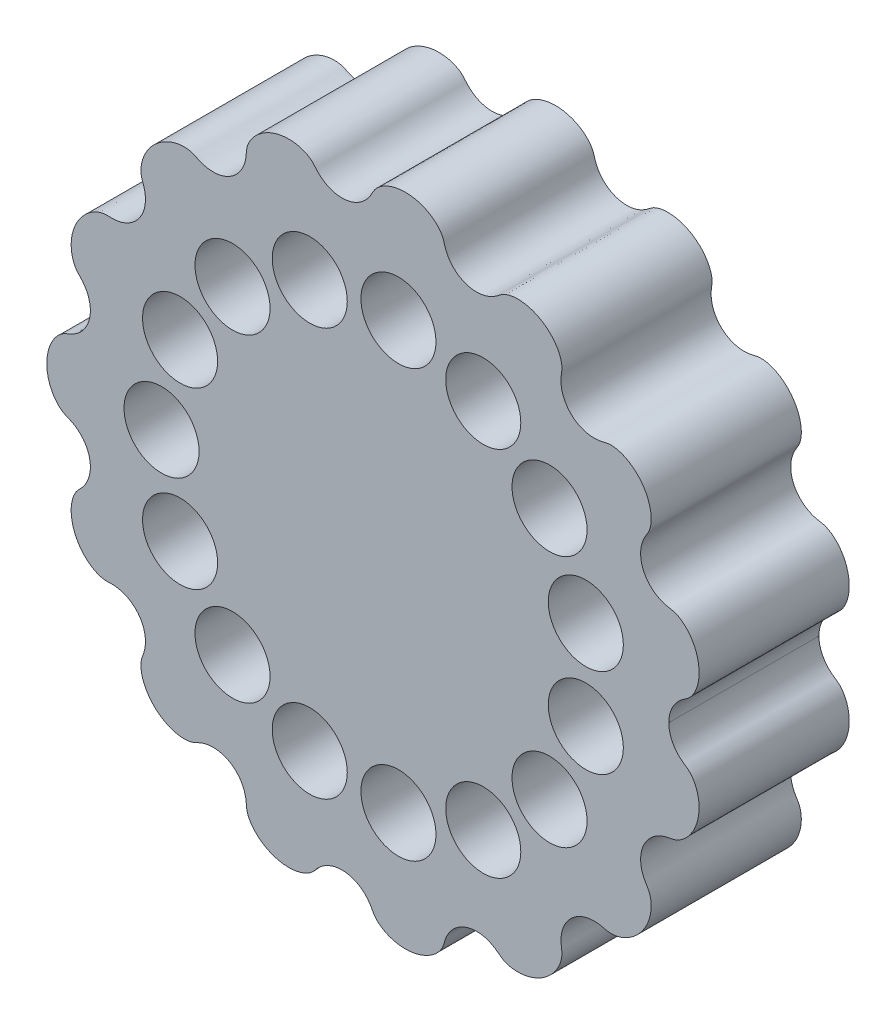
SolidWorks part; units mm, degrees
material "ABS"
ref_plane "Front Plane" through (0, 0, 0) normal (0, 0, 1) x (1, 0, 0)
ref_plane "Top Plane" through (0, 0, 0) normal (0, 1, 0) x (1, 0, 0)
ref_plane "Right Plane" through (0, 0, 0) normal (1, 0, 0) x (0, 0, -1)
sketch "Sketch2" plane through (0, 0, 0) normal (0, 0, 1) x (1, 0, 0)
  line L0 (0, 0) -> (18.3781, 0) construction
  line L1 (0, 0) -> (-12.7, 0) construction
  line L6 (0, 0) -> (-26.7529, 0) construction
  circle A0 centre (0, 0) radius 9
  circle A1 centre (-12.7, 0) radius 2.2225
  circle A10 centre (-11.602, 5.1656) radius 2.2225
  circle A11 centre (-8.498, 9.4379) radius 2.2225
  circle A12 centre (-3.9245, 12.0784) radius 2.2225
  circle A13 centre (1.3275, 12.6304) radius 2.2225
  circle A14 centre (6.35, 10.9985) radius 2.2225
  circle A15 centre (10.2745, 7.4649) radius 2.2225
  circle A16 centre (12.4225, 2.6405) radius 2.2225
  circle A17 centre (12.4225, -2.6405) radius 2.2225
  circle A18 centre (10.2745, -7.4649) radius 2.2225
  circle A19 centre (6.35, -10.9985) radius 2.2225
  circle A20 centre (1.3275, -12.6304) radius 2.2225
  circle A21 centre (-3.9245, -12.0784) radius 2.2225
  circle A22 centre (-8.498, -9.4379) radius 2.2225
  circle A23 centre (-11.602, -5.1656) radius 2.2225
  spline S0 degree 4 poles (18.7633, 4.8586) (18.8566, 4.6949) (19.0126, 4.3502) (19.1295, 3.8883) (19.146, 3.3193) (19.0772, 2.8818) (18.9864, 2.5766) (18.8762, 2.3288) (18.7622, 2.1358) (18.6445, 1.9821) (18.5309, 1.8645) (18.4127, 1.7724) (18.2984, 1.6976) (18.1631, 1.6053) (18.0131, 1.4864) (17.8313, 1.3119) (17.6678, 1.103) (17.5417, 0.8858) (17.4501, 0.6688) (17.4009, 0.5099) (17.3699, 0.3735) (17.3511, 0.2546) (17.3405, 0.1491) (17.3351, 0.0404) (17.335, -0.0379) (17.3404, -0.1482) (17.3511, -0.2558) (17.3711, -0.3808) (17.4057, -0.5292) (17.4608, -0.6993) (17.5431, -0.8835) (17.6435, -1.0585) (17.7605, -1.2214) (17.8868, -1.3648) (18.0188, -1.4893) (18.152, -1.5968) (18.284, -1.6887) (18.4068, -1.7677) (18.5101, -1.8484) (18.6114, -1.9469) (18.7103, -2.0649) (18.8119, -2.2151) (18.9788, -2.5318) (19.1284, -3.0222) (19.1691, -3.6778) (19.0197, -4.3616) (18.7658, -4.895) (18.5029, -5.2499) (18.2908, -5.4667) (18.0909, -5.625) (17.936, -5.7218) (17.7996, -5.7887) (17.6725, -5.8365) (17.5499, -5.8688) (17.4098, -5.8911) (17.2557, -5.9192) (17.0952, -5.96) (16.9297, -6.0153) (16.7182, -6.1072) (16.4691, -6.2552) (16.2082, -6.4745) (15.9606, -6.7851) (15.777, -7.1489) (15.6723, -7.5479) (15.6565, -7.9135) (15.698, -8.2228) (15.7641, -8.4609) (15.8302, -8.6338) (15.9057, -8.7908) (15.9865, -8.9326) (16.0678, -9.0566) (16.1353, -9.1714) (16.1945, -9.3026) (16.2418, -9.4503) (16.2782, -9.6273) (16.3107, -9.9874) (16.2563, -10.505) (16.0255, -11.1471) (15.5906, -11.7382) (15.1094, -12.1391) (14.6943, -12.3573) (14.4005, -12.4606) (14.1434, -12.5135) (13.9574, -12.5296) (13.7955, -12.524) (13.646, -12.4991) (13.511, -12.464) (13.3614, -12.4266) (13.1944, -12.3981) (13.0154, -12.381) (12.8253, -12.3797) (12.5738, -12.4026) (12.2655, -12.4754) (11.9355, -12.6193) (11.6068, -12.8541) (11.3394, -13.1429) (11.1399, -13.4677) (11.021, -13.7866) (10.9639, -14.0781) (10.9493, -14.3167) (10.9547, -14.4996) (10.9719, -14.6649) (10.9953, -14.8125) (11.0138, -14.9707) (11.0079, -15.1399) (10.9777, -15.3255) (10.9213, -15.5246) (10.826, -15.7601) (10.6793, -16.0232) (10.4202, -16.3707) (10.0022, -16.7545) (9.5088, -17.0394) (8.9674, -17.2095) (8.5368, -17.2602) (8.2356, -17.2556) (7.9841, -17.2204) (7.7834, -17.1697) (7.6075, -17.1031) (7.4581, -17.0235) (7.3304, -16.9284) (7.2142, -16.8343) (7.0797, -16.7369) (6.924, -16.6408) (6.7101, -16.534) (6.4291, -16.4378) (6.0935, -16.3813) (5.7124, -16.3917) (5.3285, -16.4789) (4.9609, -16.6461) (4.6712, -16.86) (4.454, -17.0906) (4.3085, -17.2969) (4.2145, -17.4622) (4.1399, -17.6257) (4.0811, -17.7846) (4.0386, -17.9329) (4.0016, -18.0673) (3.9484, -18.2093) (3.8722, -18.3523) (3.7653, -18.5053) (3.5909, -18.7015) (3.3546, -18.9043) (2.9581, -19.1547) (2.3703, -19.371) (1.6409, -19.4521) (0.9694, -19.3309) (0.494, -19.1192) (0.1984, -18.911) (0.0633, -18.791) (-0.0409, -18.6762) (-0.125, -18.5593) (-0.1906, -18.4434) (-0.2573, -18.311) (-0.3397, -18.1701) (-0.438, -18.0263) (-0.5547, -17.8825) (-0.7278, -17.7063) (-0.975, -17.5157) (-1.2995, -17.3465) (-1.6974, -17.2377) (-2.1042, -17.2148) (-2.4971, -17.274) (-2.8174, -17.3902) (-3.0701, -17.532) (-3.2554, -17.6692) (-3.3861, -17.7848) (-3.5017, -17.9035) (-3.6031, -18.0229) (-3.6924, -18.133) (-3.7817, -18.2231) (-3.8867, -18.3093) (-4.0128, -18.3939) (-4.1741, -18.4797) (-4.4111, -18.5737) (-4.7049, -18.6489) (-5.1436, -18.6992) (-5.7326, -18.6523) (-6.3023, -18.4708) (-6.8174, -18.1627) (-7.1549, -17.854) (-7.3507, -17.6166) (-7.4876, -17.3991) (-7.5669, -17.236) (-7.6196, -17.0913) (-7.6543, -16.9544) (-7.6725, -16.8247) (-7.6795, -16.6788) (-7.6932, -16.5185) (-7.7196, -16.3494) (-7.7615, -16.1729) (-7.8384, -15.9445) (-7.9726, -15.6719) (-8.1825, -15.3834) (-8.486, -15.1097) (-8.8424, -14.9039) (-9.2312, -14.778) (-9.586, -14.7404) (-9.8891, -14.7605) (-10.1254, -14.8081) (-10.2992, -14.8601) (-10.4589, -14.9217) (-10.6045, -14.9901) (-10.7343, -15.0569) (-10.8558, -15.106) (-10.9917, -15.1445) (-11.1433, -15.1711) (-11.3243, -15.184) (-11.5811, -15.1742) (-11.8846, -15.1233) (-12.3207, -14.9854) (-12.845, -14.6933) (-13.2871, -14.2907) (-13.6221, -13.8041) (-13.798, -13.399) (-13.8798, -13.107) (-13.9168, -12.8547) (-13.9232, -12.6721) (-13.913, -12.5206) (-13.8908, -12.3866) (-13.8575, -12.2643) (-13.8068, -12.1318) (-13.7541, -11.9843) (-13.7091, -11.8249) (-13.6743, -11.6539) (-13.6481, -11.4248) (-13.6517, -11.135) (-13.7112, -10.7995) (-13.8564, -10.4297) (-14.0796, -10.0888) (-14.3728, -9.7987) (-14.6815, -9.6022) (-14.9702, -9.4834) (-15.2094, -9.4216) (-15.3922, -9.3924) (-15.5659, -9.3793) (-15.7291, -9.3784) (-15.8771, -9.3868) (-16.0104, -9.3879) (-16.1536, -9.3736) (-16.3051, -9.3407) (-16.4766, -9.2837) (-16.8047, -9.1318) (-17.2258, -8.8259) (-17.6664, -8.3049) (-17.9609, -7.6328) (-18.0675, -7.0156) (-18.0489, -6.547) (-17.9914, -6.2409) (-17.9088, -5.9918) (-17.8296, -5.8227) (-17.7439, -5.6853) (-17.661, -5.5845) (-17.5943, -5.5141) (-17.5308, -5.4492) (-17.4724, -5.3879) (-17.4019, -5.309) (-17.3219, -5.2104) (-17.23, -5.0812) (-17.1338, -4.9172) (-17.0279, -4.688) (-16.9368, -4.3846) (-16.8964, -4.0268) (-16.9354, -3.6248) (-17.0518, -3.2488) (-17.2333, -2.9135) (-17.4501, -2.6512) (-17.6739, -2.4559) (-17.8733, -2.324) (-18.0344, -2.2373) (-18.1861, -2.1695) (-18.3256, -2.1159) (-18.4719, -2.0529) (-18.6155, -1.9632) (-18.7611, -1.8442) (-18.9053, -1.6958) (-19.0616, -1.4955) (-19.192, -1.2774) (-19.2944, -1.0552) (-19.3719, -0.8334) (-19.4214, -0.6522) (-19.4539, -0.4901) (-19.4739, -0.3535) (-19.4855, -0.2338) (-19.4917, -0.1326) (-19.4948, -0.037) (-19.4948, 0.0364) (-19.4917, 0.1316) (-19.4856, 0.232) (-19.4742, 0.351) (-19.4544, 0.4867) (-19.4225, 0.6475) (-19.3737, 0.8276) (-19.2973, 1.048) (-19.1964, 1.2688) (-19.0681, 1.4857) (-18.9143, 1.6852) (-18.7725, 1.8335) (-18.6329, 1.9498) (-18.5003, 2.0363) (-18.3706, 2.0977) (-18.2504, 2.1445) (-18.1062, 2.2036) (-17.9419, 2.2842) (-17.733, 2.4112) (-17.4958, 2.6047) (-17.2705, 2.8611) (-17.0558, 3.2276) (-16.9099, 3.6914) (-16.895, 4.0854) (-16.9436, 4.3777) (-16.984, 4.5249) knots 0 0 0 0 0 0.009284 0.018569 0.023211 0.027854 0.031033 0.034213 0.036543 0.038874 0.040556 0.042237 0.043918 0.0456 0.048628 0.051656 0.056303 0.058626 0.060948 0.063272 0.064433 0.065595 0.066886 0.068176 0.069432 0.070688 0.071943 0.073199 0.07572 0.07824 0.080694 0.083148 0.08563 0.088113 0.090095 0.092076 0.094058 0.09604 0.097282 0.098525 0.10101 0.103607 0.106204 0.116127 0.126049 0.135533 0.140274 0.145016 0.147725 0.150434 0.152813 0.154002 0.155191 0.157122 0.159052 0.160982 0.162912 0.165276 0.167641 0.172327 0.177141 0.181961 0.187087 0.192259 0.197312 0.199858 0.202403 0.204413 0.206423 0.208433 0.210443 0.211712 0.212982 0.21552 0.21806 0.2206 0.230761 0.24092 0.251197 0.256273 0.261349 0.26392 0.26649 0.269181 0.270527 0.271873 0.273958 0.276043 0.278128 0.280213 0.282806 0.285398 0.290549 0.295754 0.300413 0.305158 0.309821 0.314419 0.31708 0.319741 0.321582 0.323422 0.325263 0.327104 0.329419 0.331734 0.334508 0.337282 0.34191 0.346537 0.355792 0.365046 0.369673 0.374301 0.377075 0.379849 0.382164 0.384479 0.38632 0.388161 0.390001 0.391842 0.394503 0.397165 0.401762 0.406425 0.41117 0.415829 0.421034 0.426185 0.428777 0.43137 0.433455 0.43554 0.437625 0.439711 0.441056 0.442402 0.445093 0.447663 0.450234 0.45531 0.460386 0.470663 0.480822 0.490983 0.493523 0.496063 0.498601 0.499871 0.50114 0.50315 0.50516 0.50717 0.50918 0.511725 0.514271 0.519324 0.524496 0.529623 0.534442 0.539256 0.543942 0.546307 0.548671 0.550601 0.552531 0.554461 0.556392 0.557581 0.55877 0.561149 0.563858 0.566567 0.571309 0.57605 0.585534 0.595456 0.600418 0.605379 0.607976 0.610573 0.613058 0.614301 0.615543 0.617525 0.619507 0.621488 0.62347 0.625953 0.628436 0.633343 0.638384 0.643407 0.648429 0.653471 0.658378 0.660861 0.663343 0.665325 0.667307 0.669288 0.67127 0.672513 0.673755 0.676241 0.678838 0.681434 0.686396 0.691357 0.701279 0.710763 0.715505 0.720246 0.722955 0.725664 0.728043 0.729232 0.730422 0.732352 0.734282 0.736212 0.738142 0.740507 0.742871 0.747557 0.752371 0.757191 0.762317 0.76749 0.772543 0.775088 0.777634 0.779644 0.781654 0.783663 0.785673 0.786943 0.788212 0.790751 0.793291 0.79583 0.805991 0.816151 0.826427 0.831503 0.83658 0.83915 0.841721 0.844412 0.845757 0.847103 0.848145 0.849188 0.85023 0.851273 0.853358 0.855443 0.858036 0.860629 0.865779 0.870984 0.875643 0.880389 0.885051 0.889649 0.89231 0.894972 0.896812 0.898653 0.900493 0.902334 0.904649 0.906964 0.909738 0.912513 0.91714 0.919454 0.921767 0.924081 0.926394 0.927551 0.928708 0.929865 0.931022 0.93217 0.933319 0.934467 0.935616 0.937913 0.94021 0.942507 0.944804 0.949398 0.952146 0.954894 0.957192 0.95949 0.961079 0.962667 0.964255 0.965844 0.968759 0.971674 0.976278 0.980873 0.985473 0.99248 1 1 1 1 1 construction
  spline S1 degree 4 poles (17.3355, 0) (17.3355, -0.022) (17.3364, -0.0661) (17.3404, -0.1482) (17.3511, -0.2558) (17.3711, -0.3808) (17.4057, -0.5292) (17.4608, -0.6993) (17.5431, -0.8835) (17.6435, -1.0585) (17.7605, -1.2214) (17.8868, -1.3648) (18.0188, -1.4893) (18.152, -1.5968) (18.284, -1.6887) (18.4068, -1.7677) (18.5101, -1.8484) (18.6114, -1.9469) (18.7103, -2.0649) (18.8119, -2.2151) (18.9788, -2.5318) (19.1284, -3.0222) (19.1691, -3.6778) (19.0197, -4.3616) (18.7658, -4.895) (18.5029, -5.2499) (18.2908, -5.4667) (18.0909, -5.625) (17.936, -5.7218) (17.7996, -5.7887) (17.6725, -5.8365) (17.5499, -5.8688) (17.4098, -5.8911) (17.2557, -5.9192) (17.0952, -5.96) (16.9297, -6.0153) (16.7182, -6.1072) (16.4691, -6.2552) (16.2082, -6.4745) (15.9606, -6.7851) (15.777, -7.1489) (15.6723, -7.5479) (15.6565, -7.9135) (15.698, -8.2228) (15.7641, -8.4609) (15.8302, -8.6338) (15.9057, -8.7908) (15.9865, -8.9326) (16.0678, -9.0566) (16.1353, -9.1714) (16.1945, -9.3026) (16.2418, -9.4503) (16.2782, -9.6273) (16.3107, -9.9874) (16.2563, -10.505) (16.0255, -11.1471) (15.5906, -11.7382) (15.1094, -12.1391) (14.6943, -12.3573) (14.4005, -12.4606) (14.1434, -12.5135) (13.9574, -12.5296) (13.7955, -12.524) (13.646, -12.4991) (13.511, -12.464) (13.3614, -12.4266) (13.1944, -12.3981) (13.0154, -12.381) (12.8253, -12.3797) (12.5738, -12.4026) (12.2655, -12.4754) (11.9355, -12.6193) (11.6068, -12.8541) (11.3394, -13.1429) (11.1399, -13.4677) (11.021, -13.7866) (10.9639, -14.0781) (10.9493, -14.3167) (10.9547, -14.4996) (10.9719, -14.6649) (10.9953, -14.8125) (11.0138, -14.9707) (11.0079, -15.1399) (10.9777, -15.3255) (10.9213, -15.5246) (10.826, -15.7601) (10.6793, -16.0232) (10.4202, -16.3707) (10.0022, -16.7545) (9.5088, -17.0394) (8.9674, -17.2095) (8.5368, -17.2602) (8.2356, -17.2556) (7.9841, -17.2204) (7.7834, -17.1697) (7.6075, -17.1031) (7.4581, -17.0235) (7.3304, -16.9284) (7.2142, -16.8343) (7.0797, -16.7369) (6.924, -16.6408) (6.7101, -16.534) (6.4291, -16.4378) (6.0935, -16.3813) (5.7124, -16.3917) (5.3285, -16.4789) (4.9609, -16.6461) (4.6712, -16.86) (4.454, -17.0906) (4.3085, -17.2969) (4.2145, -17.4622) (4.1399, -17.6257) (4.0811, -17.7846) (4.0386, -17.9329) (4.0016, -18.0673) (3.9484, -18.2093) (3.8722, -18.3523) (3.7653, -18.5053) (3.5909, -18.7015) (3.3546, -18.9043) (2.9581, -19.1547) (2.3703, -19.371) (1.6409, -19.4521) (0.9694, -19.3309) (0.494, -19.1192) (0.1984, -18.911) (0.0633, -18.791) (-0.0409, -18.6762) (-0.125, -18.5593) (-0.1906, -18.4434) (-0.2573, -18.311) (-0.3397, -18.1701) (-0.438, -18.0263) (-0.5547, -17.8825) (-0.7278, -17.7063) (-0.975, -17.5157) (-1.2995, -17.3465) (-1.6974, -17.2377) (-2.1042, -17.2148) (-2.4971, -17.274) (-2.8174, -17.3902) (-3.0701, -17.532) (-3.2554, -17.6692) (-3.3861, -17.7848) (-3.5017, -17.9035) (-3.6031, -18.0229) (-3.6924, -18.133) (-3.7817, -18.2231) (-3.8867, -18.3093) (-4.0128, -18.3939) (-4.1741, -18.4797) (-4.4111, -18.5737) (-4.7049, -18.6489) (-5.1436, -18.6992) (-5.7326, -18.6523) (-6.3023, -18.4708) (-6.8174, -18.1627) (-7.1549, -17.854) (-7.3507, -17.6166) (-7.4876, -17.3991) (-7.5669, -17.236) (-7.6196, -17.0913) (-7.6543, -16.9544) (-7.6725, -16.8247) (-7.6795, -16.6788) (-7.6932, -16.5185) (-7.7196, -16.3494) (-7.7615, -16.1729) (-7.8384, -15.9445) (-7.9726, -15.6719) (-8.1825, -15.3834) (-8.486, -15.1097) (-8.8424, -14.9039) (-9.2312, -14.778) (-9.586, -14.7404) (-9.8891, -14.7605) (-10.1254, -14.8081) (-10.2992, -14.8601) (-10.4589, -14.9217) (-10.6045, -14.9901) (-10.7343, -15.0569) (-10.8558, -15.106) (-10.9917, -15.1445) (-11.1433, -15.1711) (-11.3243, -15.184) (-11.5811, -15.1742) (-11.8846, -15.1233) (-12.3207, -14.9854) (-12.845, -14.6933) (-13.2871, -14.2907) (-13.6221, -13.8041) (-13.798, -13.399) (-13.8798, -13.107) (-13.9168, -12.8547) (-13.9232, -12.6721) (-13.913, -12.5206) (-13.8908, -12.3866) (-13.8575, -12.2643) (-13.8068, -12.1318) (-13.7541, -11.9843) (-13.7091, -11.8249) (-13.6743, -11.6539) (-13.6481, -11.4248) (-13.6517, -11.135) (-13.7112, -10.7995) (-13.8564, -10.4297) (-14.0796, -10.0888) (-14.3728, -9.7987) (-14.6815, -9.6022) (-14.9702, -9.4834) (-15.2094, -9.4216) (-15.3922, -9.3924) (-15.5659, -9.3793) (-15.7291, -9.3784) (-15.8771, -9.3868) (-16.0104, -9.3879) (-16.1536, -9.3736) (-16.3051, -9.3407) (-16.4766, -9.2837) (-16.8047, -9.1318) (-17.2258, -8.8259) (-17.6664, -8.3049) (-17.9609, -7.6328) (-18.0675, -7.0156) (-18.0489, -6.547) (-17.9914, -6.2409) (-17.9088, -5.9918) (-17.8296, -5.8227) (-17.7439, -5.6853) (-17.661, -5.5845) (-17.5943, -5.5141) (-17.5308, -5.4492) (-17.4724, -5.3879) (-17.4019, -5.309) (-17.3219, -5.2104) (-17.23, -5.0812) (-17.1338, -4.9172) (-17.0279, -4.688) (-16.9368, -4.3846) (-16.8964, -4.0268) (-16.9354, -3.6248) (-17.0518, -3.2488) (-17.2333, -2.9135) (-17.4501, -2.6512) (-17.6739, -2.4559) (-17.8733, -2.324) (-18.0344, -2.2373) (-18.1861, -2.1695) (-18.3256, -2.1159) (-18.4719, -2.0529) (-18.6155, -1.9632) (-18.7611, -1.8442) (-18.9053, -1.6958) (-19.0616, -1.4955) (-19.192, -1.2774) (-19.2944, -1.0552) (-19.3719, -0.8334) (-19.4214, -0.6522) (-19.4539, -0.4901) (-19.4739, -0.3535) (-19.4855, -0.2338) (-19.4917, -0.1326) (-19.494, -0.0608) (-19.4945, -0.0203) (-19.4945, 0) knots 0.068176 0.068176 0.068176 0.068176 0.068176 0.069432 0.070688 0.071943 0.073199 0.07572 0.07824 0.080694 0.083148 0.08563 0.088113 0.090095 0.092076 0.094058 0.09604 0.097282 0.098525 0.10101 0.103607 0.106204 0.116127 0.126049 0.135533 0.140274 0.145016 0.147725 0.150434 0.152813 0.154002 0.155191 0.157122 0.159052 0.160982 0.162912 0.165276 0.167641 0.172327 0.177141 0.181961 0.187087 0.192259 0.197312 0.199858 0.202403 0.204413 0.206423 0.208433 0.210443 0.211712 0.212982 0.21552 0.21806 0.2206 0.230761 0.24092 0.251197 0.256273 0.261349 0.26392 0.26649 0.269181 0.270527 0.271873 0.273958 0.276043 0.278128 0.280213 0.282806 0.285398 0.290549 0.295754 0.300413 0.305158 0.309821 0.314419 0.31708 0.319741 0.321582 0.323422 0.325263 0.327104 0.329419 0.331734 0.334508 0.337282 0.34191 0.346537 0.355792 0.365046 0.369673 0.374301 0.377075 0.379849 0.382164 0.384479 0.38632 0.388161 0.390001 0.391842 0.394503 0.397165 0.401762 0.406425 0.41117 0.415829 0.421034 0.426185 0.428777 0.43137 0.433455 0.43554 0.437625 0.439711 0.441056 0.442402 0.445093 0.447663 0.450234 0.45531 0.460386 0.470663 0.480822 0.490983 0.493523 0.496063 0.498601 0.499871 0.50114 0.50315 0.50516 0.50717 0.50918 0.511725 0.514271 0.519324 0.524496 0.529623 0.534442 0.539256 0.543942 0.546307 0.548671 0.550601 0.552531 0.554461 0.556392 0.557581 0.55877 0.561149 0.563858 0.566567 0.571309 0.57605 0.585534 0.595456 0.600418 0.605379 0.607976 0.610573 0.613058 0.614301 0.615543 0.617525 0.619507 0.621488 0.62347 0.625953 0.628436 0.633343 0.638384 0.643407 0.648429 0.653471 0.658378 0.660861 0.663343 0.665325 0.667307 0.669288 0.67127 0.672513 0.673755 0.676241 0.678838 0.681434 0.686396 0.691357 0.701279 0.710763 0.715505 0.720246 0.722955 0.725664 0.728043 0.729232 0.730422 0.732352 0.734282 0.736212 0.738142 0.740507 0.742871 0.747557 0.752371 0.757191 0.762317 0.76749 0.772543 0.775088 0.777634 0.779644 0.781654 0.783663 0.785673 0.786943 0.788212 0.790751 0.793291 0.79583 0.805991 0.816151 0.826427 0.831503 0.83658 0.83915 0.841721 0.844412 0.845757 0.847103 0.848145 0.849188 0.85023 0.851273 0.853358 0.855443 0.858036 0.860629 0.865779 0.870984 0.875643 0.880389 0.885051 0.889649 0.89231 0.894972 0.896812 0.898653 0.900493 0.902334 0.904649 0.906964 0.909738 0.912513 0.91714 0.919454 0.921767 0.924081 0.926394 0.927551 0.928708 0.929865 0.931022 0.931022 0.931022 0.931022 0.931022
  spline S2 degree 4 poles (17.3355, 0) (17.3355, 0.022) (17.3364, 0.0661) (17.3404, 0.1482) (17.3511, 0.2558) (17.3711, 0.3808) (17.4057, 0.5292) (17.4608, 0.6993) (17.5431, 0.8835) (17.6435, 1.0585) (17.7605, 1.2214) (17.8868, 1.3648) (18.0188, 1.4893) (18.152, 1.5968) (18.284, 1.6887) (18.4068, 1.7677) (18.5101, 1.8484) (18.6114, 1.9469) (18.7103, 2.0649) (18.8119, 2.2151) (18.9788, 2.5318) (19.1284, 3.0222) (19.1691, 3.6778) (19.0197, 4.3616) (18.7658, 4.895) (18.5029, 5.2499) (18.2908, 5.4667) (18.0909, 5.625) (17.936, 5.7218) (17.7996, 5.7887) (17.6725, 5.8365) (17.5499, 5.8688) (17.4098, 5.8911) (17.2557, 5.9192) (17.0952, 5.96) (16.9297, 6.0153) (16.7182, 6.1072) (16.4691, 6.2552) (16.2082, 6.4745) (15.9606, 6.7851) (15.777, 7.1489) (15.6723, 7.5479) (15.6565, 7.9135) (15.698, 8.2228) (15.7641, 8.4609) (15.8302, 8.6338) (15.9057, 8.7908) (15.9865, 8.9326) (16.0678, 9.0566) (16.1353, 9.1714) (16.1945, 9.3026) (16.2418, 9.4503) (16.2782, 9.6273) (16.3107, 9.9874) (16.2563, 10.505) (16.0255, 11.1471) (15.5906, 11.7382) (15.1094, 12.1391) (14.6943, 12.3573) (14.4005, 12.4606) (14.1434, 12.5135) (13.9574, 12.5296) (13.7955, 12.524) (13.646, 12.4991) (13.511, 12.464) (13.3614, 12.4266) (13.1944, 12.3981) (13.0154, 12.381) (12.8253, 12.3797) (12.5738, 12.4026) (12.2655, 12.4754) (11.9355, 12.6193) (11.6068, 12.8541) (11.3394, 13.1429) (11.1399, 13.4677) (11.021, 13.7866) (10.9639, 14.0781) (10.9493, 14.3167) (10.9547, 14.4996) (10.9719, 14.6649) (10.9953, 14.8125) (11.0138, 14.9707) (11.0079, 15.1399) (10.9777, 15.3255) (10.9213, 15.5246) (10.826, 15.7601) (10.6793, 16.0232) (10.4202, 16.3707) (10.0022, 16.7545) (9.5088, 17.0394) (8.9674, 17.2095) (8.5368, 17.2602) (8.2356, 17.2556) (7.9841, 17.2204) (7.7834, 17.1697) (7.6075, 17.1031) (7.4581, 17.0235) (7.3304, 16.9284) (7.2142, 16.8343) (7.0797, 16.7369) (6.924, 16.6408) (6.7101, 16.534) (6.4291, 16.4378) (6.0935, 16.3813) (5.7124, 16.3917) (5.3285, 16.4789) (4.9609, 16.6461) (4.6712, 16.86) (4.454, 17.0906) (4.3085, 17.2969) (4.2145, 17.4622) (4.1399, 17.6257) (4.0811, 17.7846) (4.0386, 17.9329) (4.0016, 18.0673) (3.9484, 18.2093) (3.8722, 18.3523) (3.7653, 18.5053) (3.5909, 18.7015) (3.3546, 18.9043) (2.9581, 19.1547) (2.3703, 19.371) (1.6409, 19.4521) (0.9694, 19.3309) (0.494, 19.1192) (0.1984, 18.911) (0.0633, 18.791) (-0.0409, 18.6762) (-0.125, 18.5593) (-0.1906, 18.4434) (-0.2573, 18.311) (-0.3397, 18.1701) (-0.438, 18.0263) (-0.5547, 17.8825) (-0.7278, 17.7063) (-0.975, 17.5157) (-1.2995, 17.3465) (-1.6974, 17.2377) (-2.1042, 17.2148) (-2.4971, 17.274) (-2.8174, 17.3902) (-3.0701, 17.532) (-3.2554, 17.6692) (-3.3861, 17.7848) (-3.5017, 17.9035) (-3.6031, 18.0229) (-3.6924, 18.133) (-3.7817, 18.2231) (-3.8867, 18.3093) (-4.0128, 18.3939) (-4.1741, 18.4797) (-4.4111, 18.5737) (-4.7049, 18.6489) (-5.1436, 18.6992) (-5.7326, 18.6523) (-6.3023, 18.4708) (-6.8174, 18.1627) (-7.1549, 17.854) (-7.3507, 17.6166) (-7.4876, 17.3991) (-7.5669, 17.236) (-7.6196, 17.0913) (-7.6543, 16.9544) (-7.6725, 16.8247) (-7.6795, 16.6788) (-7.6932, 16.5185) (-7.7196, 16.3494) (-7.7615, 16.1729) (-7.8384, 15.9445) (-7.9726, 15.6719) (-8.1825, 15.3834) (-8.486, 15.1097) (-8.8424, 14.9039) (-9.2312, 14.778) (-9.586, 14.7404) (-9.8891, 14.7605) (-10.1254, 14.8081) (-10.2992, 14.8601) (-10.4589, 14.9217) (-10.6045, 14.9901) (-10.7343, 15.0569) (-10.8558, 15.106) (-10.9917, 15.1445) (-11.1433, 15.1711) (-11.3243, 15.184) (-11.5811, 15.1742) (-11.8846, 15.1233) (-12.3207, 14.9854) (-12.845, 14.6933) (-13.2871, 14.2907) (-13.6221, 13.8041) (-13.798, 13.399) (-13.8798, 13.107) (-13.9168, 12.8547) (-13.9232, 12.6721) (-13.913, 12.5206) (-13.8908, 12.3866) (-13.8575, 12.2643) (-13.8068, 12.1318) (-13.7541, 11.9843) (-13.7091, 11.8249) (-13.6743, 11.6539) (-13.6481, 11.4248) (-13.6517, 11.135) (-13.7112, 10.7995) (-13.8564, 10.4297) (-14.0796, 10.0888) (-14.3728, 9.7987) (-14.6815, 9.6022) (-14.9702, 9.4834) (-15.2094, 9.4216) (-15.3922, 9.3924) (-15.5659, 9.3793) (-15.7291, 9.3784) (-15.8771, 9.3868) (-16.0104, 9.3879) (-16.1536, 9.3736) (-16.3051, 9.3407) (-16.4766, 9.2837) (-16.8047, 9.1318) (-17.2258, 8.8259) (-17.6664, 8.3049) (-17.9609, 7.6328) (-18.0675, 7.0156) (-18.0489, 6.547) (-17.9914, 6.2409) (-17.9088, 5.9918) (-17.8296, 5.8227) (-17.7439, 5.6853) (-17.661, 5.5845) (-17.5943, 5.5141) (-17.5308, 5.4492) (-17.4724, 5.3879) (-17.4019, 5.309) (-17.3219, 5.2104) (-17.23, 5.0812) (-17.1338, 4.9172) (-17.0279, 4.688) (-16.9368, 4.3846) (-16.8964, 4.0268) (-16.9354, 3.6248) (-17.0518, 3.2488) (-17.2333, 2.9135) (-17.4501, 2.6512) (-17.6739, 2.4559) (-17.8733, 2.324) (-18.0344, 2.2373) (-18.1861, 2.1695) (-18.3256, 2.1159) (-18.4719, 2.0529) (-18.6155, 1.9632) (-18.7611, 1.8442) (-18.9053, 1.6958) (-19.0616, 1.4955) (-19.192, 1.2774) (-19.2944, 1.0552) (-19.3719, 0.8334) (-19.4214, 0.6522) (-19.4539, 0.4901) (-19.4739, 0.3535) (-19.4855, 0.2338) (-19.4917, 0.1326) (-19.494, 0.0608) (-19.4945, 0.0203) (-19.4945, 0) knots 0.068176 0.068176 0.068176 0.068176 0.068176 0.069432 0.070688 0.071943 0.073199 0.07572 0.07824 0.080694 0.083148 0.08563 0.088113 0.090095 0.092076 0.094058 0.09604 0.097282 0.098525 0.10101 0.103607 0.106204 0.116127 0.126049 0.135533 0.140274 0.145016 0.147725 0.150434 0.152813 0.154002 0.155191 0.157122 0.159052 0.160982 0.162912 0.165276 0.167641 0.172327 0.177141 0.181961 0.187087 0.192259 0.197312 0.199858 0.202403 0.204413 0.206423 0.208433 0.210443 0.211712 0.212982 0.21552 0.21806 0.2206 0.230761 0.24092 0.251197 0.256273 0.261349 0.26392 0.26649 0.269181 0.270527 0.271873 0.273958 0.276043 0.278128 0.280213 0.282806 0.285398 0.290549 0.295754 0.300413 0.305158 0.309821 0.314419 0.31708 0.319741 0.321582 0.323422 0.325263 0.327104 0.329419 0.331734 0.334508 0.337282 0.34191 0.346537 0.355792 0.365046 0.369673 0.374301 0.377075 0.379849 0.382164 0.384479 0.38632 0.388161 0.390001 0.391842 0.394503 0.397165 0.401762 0.406425 0.41117 0.415829 0.421034 0.426185 0.428777 0.43137 0.433455 0.43554 0.437625 0.439711 0.441056 0.442402 0.445093 0.447663 0.450234 0.45531 0.460386 0.470663 0.480822 0.490983 0.493523 0.496063 0.498601 0.499871 0.50114 0.50315 0.50516 0.50717 0.50918 0.511725 0.514271 0.519324 0.524496 0.529623 0.534442 0.539256 0.543942 0.546307 0.548671 0.550601 0.552531 0.554461 0.556392 0.557581 0.55877 0.561149 0.563858 0.566567 0.571309 0.57605 0.585534 0.595456 0.600418 0.605379 0.607976 0.610573 0.613058 0.614301 0.615543 0.617525 0.619507 0.621488 0.62347 0.625953 0.628436 0.633343 0.638384 0.643407 0.648429 0.653471 0.658378 0.660861 0.663343 0.665325 0.667307 0.669288 0.67127 0.672513 0.673755 0.676241 0.678838 0.681434 0.686396 0.691357 0.701279 0.710763 0.715505 0.720246 0.722955 0.725664 0.728043 0.729232 0.730422 0.732352 0.734282 0.736212 0.738142 0.740507 0.742871 0.747557 0.752371 0.757191 0.762317 0.76749 0.772543 0.775088 0.777634 0.779644 0.781654 0.783663 0.785673 0.786943 0.788212 0.790751 0.793291 0.79583 0.805991 0.816151 0.826427 0.831503 0.83658 0.83915 0.841721 0.844412 0.845757 0.847103 0.848145 0.849188 0.85023 0.851273 0.853358 0.855443 0.858036 0.860629 0.865779 0.870984 0.875643 0.880389 0.885051 0.889649 0.89231 0.894972 0.896812 0.898653 0.900493 0.902334 0.904649 0.906964 0.909738 0.912513 0.91714 0.919454 0.921767 0.924081 0.926394 0.927551 0.928708 0.929865 0.931022 0.931022 0.931022 0.931022 0.931022
  point P2 (-32.821, 10.0087)
  dimension "D1" = 18
  dimension "D2" = 4.445
  dimension "D3" = 12.7
  dimension "D4" = 15
  dimension "D5" = 12.7
extrude "Boss-Extrude1" add sketch "Sketch2" along normal blind 8.89
sketch "Sketch3" plane through (0, 0, 8.89) normal (0, 0, 1) x (1, 0, 0)
  circle A0 centre (0, 0) radius 9
  circle A1 centre (0, 0) radius 9 construction
extrude "Boss-Extrude2" add sketch "Sketch3" against normal offset from surface (3.89 mm away) 5 up to face at (-1.0795, 0, 0)
